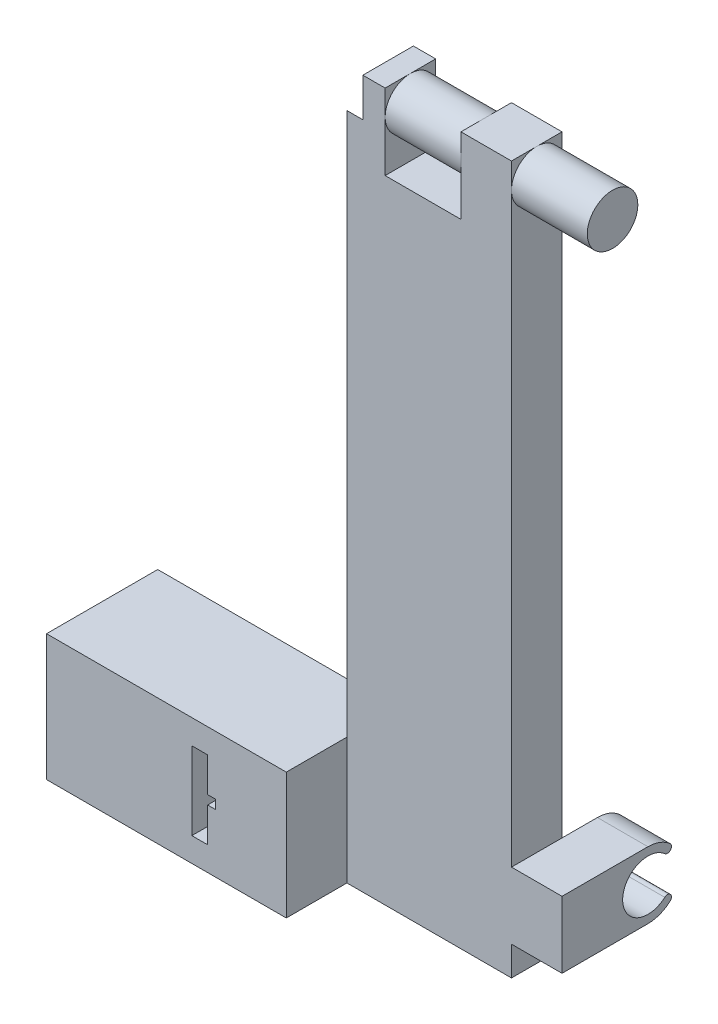
SolidWorks part; units mm, degrees
note: The reader was unsure of these and kept them because the rebuilt part matched: shared geometry of "Sketch5<2>", "Sketch8<3>", "Sketch7<4>".
ref_plane "Front Plane" through (0, 0, 0) normal (0, 0, 1) x (1, 0, 0)
ref_plane "Top Plane" through (0, 0, 0) normal (0, 1, 0) x (1, 0, 0)
ref_plane "Right Plane" through (0, 0, 0) normal (1, 0, 0) x (0, 0, -1)
sketch "Sketch1" plane through (0, 0, 0) normal (0, 1, 0) x (1, 0, 0)
  line L1 (-6.35, -6.35) -> (6.35, -6.35)
  line L2 (-6.35, -6.35) -> (-6.35, 6.35)
  line L3 (-6.35, 6.35) -> (6.35, 6.35)
  line L4 (6.35, -6.35) -> (6.35, 6.35)
  line L5 (-6.35, -6.35) -> (6.35, 6.35) construction
  line L6 (-6.35, 6.35) -> (6.35, -6.35) construction
  point P0 (0, 0)
  dimension "D1" = 12.7
  dimension "D2" = 12.7
extrude "Boss-Extrude1" add sketch "Sketch1" against normal blind 177.8
sketch "Sketch2" plane through (0, 0, 0) normal (1, 0, 0) x (0, 0, -1)
  line L0 (6.35, -177.8) -> (6.35, 0) construction
  circle A0 centre (0, -6.35) radius 6.35
  dimension "D1" = 12.7
extrude "Boss-Extrude2" add sketch "Sketch2" along normal mid plane 50.8
sketch "Sketch3" plane through (-6.35, 0, 0) normal (-1, 0, 0) x (0, 0, 1)
  line L0 (-6.35, -177.8) -> (-6.35, -6.35) construction
  line L1 (6.35, -177.8) -> (-6.35, -177.8)
  line L2 (6.35, -177.8) -> (6.35, -19.05)
  line L3 (6.35, -19.05) -> (-6.35, -19.05)
  line L4 (-6.35, -177.8) -> (-6.35, -19.05)
  line L5 (0, 0) -> (6.35, 0) construction
  dimension "D1" = 19.05
extrude "Boss-Extrude3" add sketch "Sketch3" along normal up to surface (28.652 mm away)
sketch "Sketch4" plane through (-6.35, 0, 0) normal (-1, 0, 0) x (0, 0, 1)
  line L1 (6.35, -19.05) -> (-6.35, -19.05)
  line L2 (6.35, -19.05) -> (6.35, 0)
  line L3 (6.35, 0) -> (-6.35, 0)
  line L4 (-6.35, -19.05) -> (-6.35, 0)
extrude "Boss-Extrude4" add sketch "Sketch4" against normal up to surface (9.602 mm away) from surface
sketch "Sketch5" plane through (-35.002, 0, 0) normal (-1, 0, 0) x (0, 0, 1)
  line L0 (-3.833, -30.756) -> (-3.833, -16.606) construction
  line L1 (3.767, -16.606) -> (3.767, -30.756) construction
  line L2 (-3.833, -30.756) -> (-3.833, -16.606)
  line L3 (3.767, -16.606) -> (3.767, -30.756)
  line L4 (6.35, 0) -> (3.631, 0)
  line L5 (6.35, 0) -> (-6.35, 0) construction
  line L6 (6.35, 0) -> (6.35, -9.694)
  line L7 (6.35, -177.8) -> (6.35, 0) construction
  line L9 (-6.35, 0) -> (-6.35, -177.8) construction
  line L10 (-6.35, 0) -> (-3.697, 0)
  line L11 (3.631, 0) -> (-3.697, 0)
  line L14 (-6.35, -9.8138) -> (-6.35, 0)
  arc A0 (-0.533, 0.9767) -> (-2.783, 0.4522) centre (-0.033, -6.256) ccw construction
  arc A1 (-3.833, -16.606) -> (-4.5038, -13.0051) centre (-13.833, -16.606) ccw construction
  arc A2 (-3.833, -30.756) -> (3.767, -30.756) centre (-0.033, -30.756) ccw construction
  arc A3 (5.767, -10.606) -> (6.35, -9.694) centre (-0.033, -6.256) ccw
  arc A4 (-3.833, -16.606) -> (-5.833, -10.606) centre (-13.833, -16.606) ccw
  arc A5 (-3.833, -30.756) -> (3.767, -30.756) centre (-0.033, -30.756) ccw
  arc A6 (5.767, -10.606) -> (3.939, -14.7591) centre (13.767, -16.606) ccw construction
  arc A7 (5.767, -10.606) -> (3.767, -16.606) centre (13.767, -16.606) ccw
  circle A8 centre (-0.033, -26.756) radius 1.2744 construction
  circle A9 centre (-0.033, -26.756) radius 1.2744
  circle A10 centre (-0.033, -30.756) radius 1.2744 construction
  circle A11 centre (-0.033, -30.756) radius 1.2744
  arc A13 (-6.35, -9.8138) -> (-5.833, -10.606) centre (-0.033, -6.256) ccw
extrude "Cut-Extrude1" cut sketch "Sketch5" against normal up to surface (4 mm away)
extrude "Cut-Extrude2" cut sketch "Sketch5<2>" against normal blind 6.35 contours A9 | A11
sketch "Sketch5<2>" plane through (-35.002, 0, 0) normal (-1, 0, 0) x (0, 0, 1) same geometry as "Sketch5"
sketch "Sketch7" plane through (6.35, 0, 0) normal (1, 0, 0) x (0, 0, -1)
  line L0 (6.35, -170.434) -> (15.24, -170.434)
  line L1 (6.35, -153.67) -> (15.24, -153.67)
  line L2 (6.35, -177.8) -> (6.35, -6.35) construction
  line L3 (20.8136, -168.3124) -> (19.4624, -166.7947) construction
  line L4 (19.4624, -157.3093) -> (20.8136, -155.7916) construction
  line L5 (6.35, -170.434) -> (6.35, -153.67)
  line L6 (-6.35, -177.8) -> (-6.35, -6.35) construction
  line L7 (6.35, -153.67) -> (-6.35, -153.67)
  line L8 (6.35, -153.67) -> (6.35, -170.434)
  line L9 (6.35, -170.434) -> (-6.35, -170.434)
  line L10 (-6.35, -153.67) -> (-6.35, -170.434)
  line L11 (-6.35, -177.8) -> (6.35, -177.8) construction
  arc A0 (19.4624, -157.3093) -> (19.4624, -166.7947) centre (15.24, -162.052) ccw
  arc A1 (19.4624, -157.3093) -> (20.8136, -155.7916) centre (20.138, -156.5504) ccw
  arc A2 (19.4624, -166.7947) -> (20.8136, -168.3124) centre (20.138, -167.5536) cw
  arc A3 (20.8136, -155.7916) -> (15.24, -153.67) centre (15.24, -162.052) ccw
  arc A4 (20.8136, -168.3124) -> (15.24, -170.434) centre (15.24, -162.052) cw
  point P17 (20.138, -167.5536)
  point P18 (20.138, -156.5504)
  point P19 (20.8968, -157.226)
  point P20 (20.8968, -166.878)
  point P22 (8.89, -162.052)
  dimension "D1" = 6.35
  dimension "D3" = 1.016
  dimension "D2" = 9.652
  dimension "D4" = 2.54
  dimension "D5" = 15.748
sketch "Sketch8" plane through (0, 0, 6.35) normal (0, 0, 1) x (1, 0, 0)
  line L0 (6.35, -177.8) -> (6.35, -6.35) construction
  line L1 (-35.002, -177.8) -> (-95.25, -177.8)
  line L2 (-35.002, -177.8) -> (-35.002, -146.05)
  line L3 (-35.002, -146.05) -> (-95.25, -146.05)
  line L4 (-95.25, -177.8) -> (-95.25, -146.05)
  line L5 (-35.002, -177.8) -> (-44.45, -177.8)
  line L6 (-35.002, -177.8) -> (-35.002, -146.05)
  line L7 (-35.002, -146.05) -> (-44.45, -146.05)
  line L8 (-44.45, -177.8) -> (-44.45, -146.05)
  line M6 (-35.002, -9.694) -> (-35.002, -177.8)
  dimension "D1" = 31.75
  dimension "D2" = 101.6
  dimension "D3" = 50.8
extrude "Boss-Extrude5" add sketch "Sketch8" against normal up to surface (12.7 mm away) contours L4 L1 L3 M6 | L1 L8 L3 L4 up to face at (-16.016, -33.2598, -6.35)
extrude "Boss-Extrude6" add sketch "Sketch8<3>" along normal blind 15.24 contours L8 L1 L3 M6 | L1 L8 L3 L4
sketch "Sketch8<3>" plane through (0, 0, 6.35) normal (0, 0, 1) x (1, 0, 0) same geometry as "Sketch8"
sketch "Sketch9" plane through (0, 0, -6.35) normal (0, 0, -1) x (-1, 0, 0)
  line L1 (95.25, -177.8) -> (95.25, -146.05) construction
  line L2 (85.852, -151.892) -> (85.852, -146.05) construction
  line L3 (44.45, -151.892) -> (85.852, -151.892)
  line L4 (44.45, -151.892) -> (44.45, -171.958)
  line L5 (44.45, -171.958) -> (85.852, -171.958)
  line L6 (85.852, -151.892) -> (85.852, -171.958)
  line L7 (35.002, -146.05) -> (95.25, -146.05) construction
  line L8 (85.852, -171.958) -> (85.852, -177.8) construction
  line L9 (-6.35, -177.8) -> (95.25, -177.8) construction
  dimension "D1" = 20.066
  dimension "D2" = 9.398
  dimension "D3" = 41.402
extrude "Cut-Extrude3" cut sketch "Sketch9" against normal blind 21.082
extrude "Boss-Extrude7" add sketch "Sketch7" along normal blind 12.7 contours L9 L2 L7 L4 | A4 A2 A0 A1 A3 L1 L2 L0
extrude "Boss-Extrude8" add sketch "Sketch7<4>" against normal blind 12.7 from offset 25.4 contours A4 A2 A0 A1 A3 L1 L2 L0 offset against normal yes
sketch "Sketch7<4>" plane through (6.35, 0, 0) normal (1, 0, 0) x (0, 0, -1) same geometry as "Sketch7"
sketch "Sketch10" plane through (0, 0, 21.59) normal (0, 0, 1) x (1, 0, 0)
  line L0 (-58.352, -152.558) -> (-55.152, -152.558) construction
  line L1 (-55.152, -152.558) -> (-55.152, -171.358) construction
  line L2 (-55.152, -171.358) -> (-58.352, -171.358) construction
  line L3 (-58.352, -171.358) -> (-58.352, -152.558) construction
  line L4 (-53.1604, -161.208) -> (-55.152, -161.208) construction
  line L5 (-53.1604, -162.708) -> (-53.1604, -161.208) construction
  line L6 (-53.1604, -162.708) -> (-55.152, -162.708) construction
  line L7 (-55.152, -162.708) -> (-55.152, -161.208) construction
  line L8 (-54.771, -152.177) -> (-54.771, -171.739)
  line L9 (-54.771, -171.739) -> (-58.733, -171.739)
  line L10 (-58.733, -171.739) -> (-58.733, -152.177)
  line L11 (-58.733, -152.177) -> (-54.771, -152.177)
  line L12 (-52.7794, -163.089) -> (-55.152, -163.089)
  line L13 (-52.7794, -163.089) -> (-52.7794, -160.827)
  line L14 (-52.7794, -160.827) -> (-55.152, -160.827)
  line L15 (-55.152, -163.089) -> (-55.152, -160.827)
  dimension "D1" = 0.381
extrude "Cut-Extrude4" cut sketch "Sketch10" against normal through all contours L3 L2 L1 L0 | L6 L5 L4 L1 | L12 L15 L14 L8 L11 L10 L9 | L13 L14 L8 L12 | L15 L12 L8 L14
